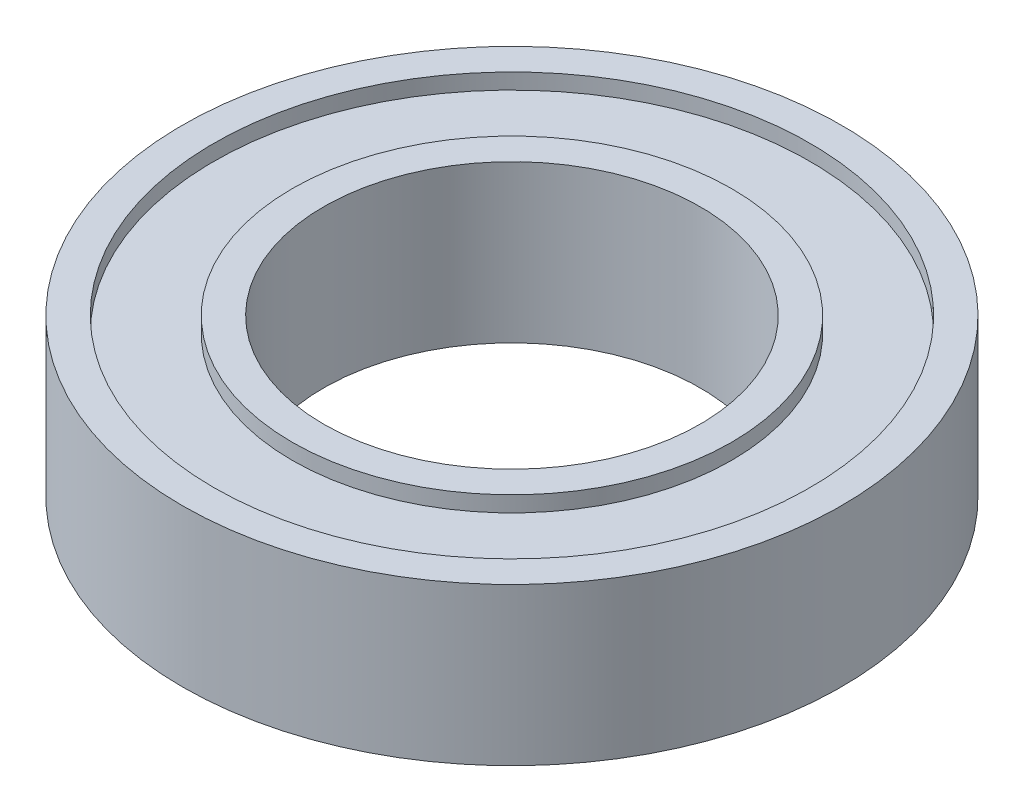
SolidWorks part; units mm, degrees
ref_plane "Plan de face" through (0, 0, 0) normal (0, 0, 1) x (1, 0, 0)
ref_plane "Plan de dessus" through (0, 0, 0) normal (0, 1, 0) x (1, 0, 0)
ref_plane "Plan de droite" through (0, 0, 0) normal (1, 0, 0) x (0, 0, -1)
sketch "Esquisse1" plane through (0, 0, 0) normal (0, 1, 0) x (1, 0, 0)
  circle A0 centre (0, 0) radius 6
  circle A1 centre (0, 0) radius 10.5
  circle A2 centre (0, 0) radius 7
  circle A3 centre (0, 0) radius 9.5
  dimension "D1" = 12
  dimension "D2" = 1
  dimension "D3" = 1
  dimension "D4" = 21
extrude "Boss.-Extru.1" add sketch "Esquisse1" along normal blind 2.5 and the other way blind 2.5 contours A2 A0 | A1 A3 region at (-10.203, 0, 0) region at (-6.802, 0, 0)
extrude "Boss.-Extru.2" add sketch "Esquisse1<3>" along normal blind 2 and the other way blind 2 contours A3 A2 region at (-9.2313, 0, 0)
sketch "Esquisse1<3>" plane through (0, 0, 0) normal (0, 1, 0) x (1, 0, 0) same geometry as "Esquisse1"
